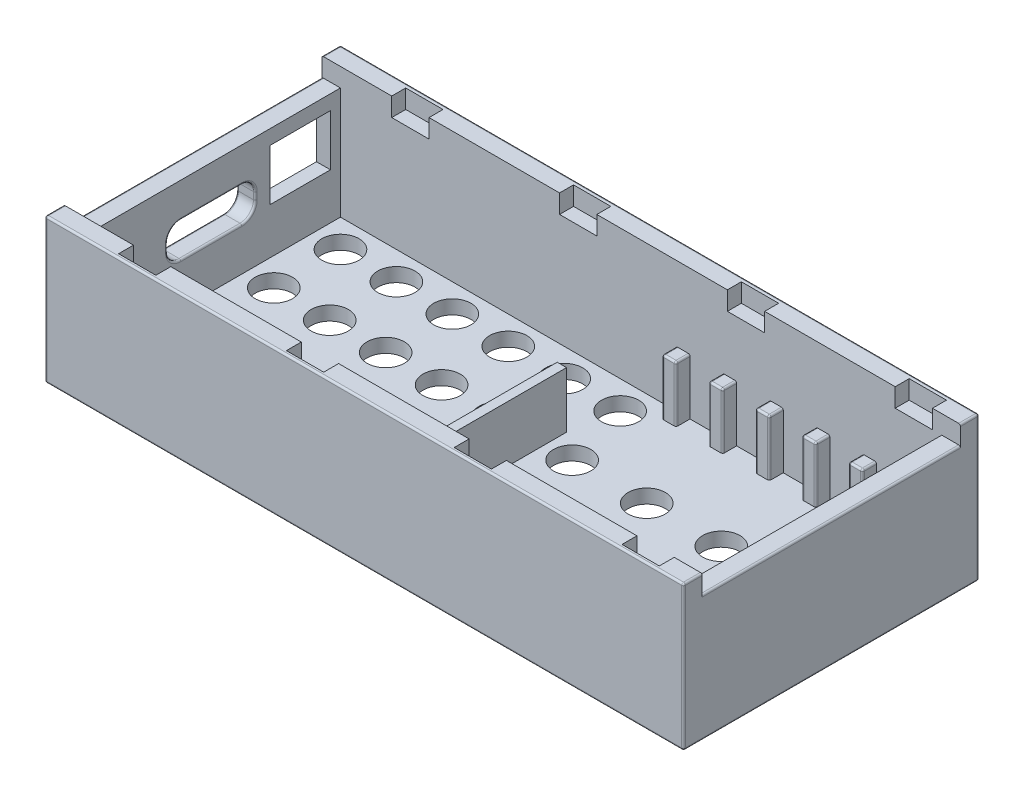
SolidWorks part; units mm, degrees
material "PLA"
ref_plane "前视基准面" through (0, 0, 0) normal (0, 0, 1) x (1, 0, 0)
ref_plane "上视基准面" through (0, 0, 0) normal (0, 1, 0) x (1, 0, 0)
ref_plane "右视基准面" through (0, 0, 0) normal (1, 0, 0) x (0, 0, -1)
sketch "草图1" plane through (0, 0, 0) normal (0, 0, 1) x (1, 0, 0)
  line L0 (0, 0) -> (68.5, 0)
  line L1 (68.5, 0) -> (68.5, 13.5)
  line L2 (68.5, 13.5) -> (66.5, 13.5)
  line L3 (66.5, 13.5) -> (66.5, 1.5)
  line L4 (66.5, 1.5) -> (2, 1.5)
  line L5 (2, 1.5) -> (2, 13.5)
  line L6 (2, 13.5) -> (0, 13.5)
  line L7 (0, 13.5) -> (0, 0)
  dimension "D1" = 64.5
  dimension "D3" = 2
  dimension "D4" = 1.5
  dimension "D6" = 12
extrude "凸台-拉伸1" add sketch "草图1" along normal blind 31.7
sketch "草图3" plane through (0, 1.5, 0) normal (0, 1, 0) x (1, 0, 0)
  line L0 (2, -31.7) -> (66.5, -31.7)
  line L1 (66.5, -31.7) -> (66.5, -29.7)
  line L2 (66.5, -31.7) -> (66.5, 0) construction
  line L3 (66.5, -29.7) -> (2, -29.7)
  line L4 (2, -31.7) -> (2, 0) construction
  line L5 (2, -29.7) -> (2, -31.7)
  dimension "D1" = 2
extrude "凸台-拉伸2" add sketch "草图3" along normal through all
sketch "草图4" plane through (0, 1.5, 0) normal (0, 1, 0) x (1, 0, 0)
  line L0 (2, 0) -> (66.5, 0)
  line L1 (66.5, -29.7) -> (66.5, 0) construction
  line L2 (66.5, -29.7) -> (66.5, 0) construction
  line L3 (66.5, 0) -> (66.5, -2)
  line L4 (66.5, -2) -> (2, -2)
  line L5 (2, -29.7) -> (2, 0) construction
  line L6 (2, -2) -> (2, 0)
  dimension "D1" = 2
extrude "凸台-拉伸3" add sketch "草图4" along normal through all
sketch "草图5" plane through (0, 1.5, 0) normal (0, 1, 0) x (1, 0, 0)
  line L0 (33.6, -6.415) -> (33.6, -25.7073) construction
  line L2 (23.9227, -15.85) -> (46.7103, -15.85) construction
  line L3 (2, -2) -> (66.5, -2) construction
  line L4 (66.5, -29.7) -> (2, -29.7) construction
  line L5 (34.1, -9.85) -> (33.1, -9.85)
  line L6 (33.1, -9.85) -> (33.1, -21.85)
  line L7 (34.1, -9.85) -> (34.1, -21.85)
  line L8 (34.1, -21.85) -> (33.1, -21.85)
  line L9 (2, -29.7) -> (2, -2) construction
  point P14 (33.6, -9.85)
  point P16 (34.1, -15.85)
  point P17 (33.1, -15.85)
  dimension "D1" = 1
  dimension "D2" = 31.6
  dimension "D3" = 12
extrude "凸台-拉伸4" add sketch "草图5" along normal blind 6 contours L6 L8 L7 L5
sketch "草图10" plane through (0, 0, 0) normal (-1, 0, 0) x (0, 0, 1)
  line L0 (5.075, 9.1862) -> (7.575, 9.1862) construction
  line L1 (5.075, 8.1862) -> (5.075, 10.1862) construction
  line L2 (7.575, 10.1862) -> (7.575, 8.1862) construction
  line L3 (6.325, 8.1862) -> (6.325, 10.1862) construction
  line L4 (7.575, 8.1862) -> (5.075, 8.1862) construction
  line L5 (5.075, 10.1862) -> (7.575, 10.1862) construction
  line L7 (8.575, 7.4362) -> (4.075, 7.4362)
  line L8 (8.575, 7.4362) -> (8.575, 10.9362)
  line L9 (8.575, 10.9362) -> (4.075, 10.9362)
  line L10 (4.075, 7.4362) -> (4.075, 10.9362)
  line L11 (8.575, 7.4362) -> (4.075, 10.9362) construction
  line L12 (8.575, 10.9362) -> (4.075, 7.4362) construction
  point P12 (6.325, 9.1862)
  dimension "D1" = 3.5
  dimension "D2" = 4.5
extrude "切除-拉伸3" cut sketch "草图10" against normal up to next
sketch "草图11" plane through (0, 0, 0) normal (-1, 0, 0) x (0, 0, 1)
  line L14 (11.13, 8.3362) -> (11.13, 7.5762)
  line L15 (12.58, 6.1262) -> (19.12, 6.1262)
  line L16 (20.57, 7.5762) -> (20.57, 8.3362)
  line L17 (19.12, 9.7862) -> (12.58, 9.7862)
  line L18 (11.13, 8.3362) -> (11.13, 7.5762)
  line L19 (12.58, 6.1262) -> (19.12, 6.1262)
  line L20 (20.57, 7.5762) -> (20.57, 8.3362)
  line L21 (19.12, 9.7862) -> (12.58, 9.7862)
  arc A8 (11.13, 7.5762) -> (12.58, 6.1262) centre (12.58, 7.5762) ccw
  arc A9 (19.12, 6.1262) -> (20.57, 7.5762) centre (19.12, 7.5762) ccw
  arc A10 (20.57, 8.3362) -> (19.12, 9.7862) centre (19.12, 8.3362) ccw
  arc A11 (12.58, 9.7862) -> (11.13, 8.3362) centre (12.58, 8.3362) ccw
  arc A12 (11.13, 7.5762) -> (12.58, 6.1262) centre (12.58, 7.5762) ccw
  arc A13 (19.12, 6.1262) -> (20.57, 7.5762) centre (19.12, 7.5762) ccw
  arc A14 (20.57, 8.3362) -> (19.12, 9.7862) centre (19.12, 8.3362) ccw
  arc A15 (12.58, 9.7862) -> (11.13, 8.3362) centre (12.58, 8.3362) ccw
  dimension "D1" = 0.3
extrude "切除-拉伸4" cut sketch "草图11" against normal up to next
sketch "草图14" plane through (0, 0, 2) normal (0, 0, 1) x (1, 0, 0)
  line L0 (64.4954, 1.5) -> (64.4954, 7.5)
  line L1 (2, 1.5) -> (66.5, 1.5) construction
  line L2 (64.4954, 7.5) -> (62.9954, 7.5)
  line L3 (62.9954, 7.5) -> (62.9954, 1.5)
  line L4 (62.9954, 1.5) -> (64.4954, 1.5)
  line L5 (66.5, 13.5) -> (66.5, 1.5) construction
  line L6 (62.1133, 1.5) -> (62.1133, 7.9181) construction
  line L7 (57.9954, 7.5) -> (57.9954, 1.5)
  line L8 (59.4954, 7.5) -> (57.9954, 7.5)
  line L9 (59.4954, 1.5) -> (59.4954, 7.5)
  line L10 (57.9954, 1.5) -> (59.4954, 1.5)
  line L11 (52.9954, 7.5) -> (52.9954, 1.5)
  line L12 (54.4954, 7.5) -> (52.9954, 7.5)
  line L13 (54.4954, 1.5) -> (54.4954, 7.5)
  line L14 (52.9954, 1.5) -> (54.4954, 1.5)
  line L15 (47.9954, 7.5) -> (47.9954, 1.5)
  line L16 (49.4954, 7.5) -> (47.9954, 7.5)
  line L17 (49.4954, 1.5) -> (49.4954, 7.5)
  line L18 (47.9954, 1.5) -> (49.4954, 1.5)
  line L19 (42.9954, 7.5) -> (42.9954, 1.5)
  line L20 (44.4954, 7.5) -> (42.9954, 7.5)
  line L21 (44.4954, 1.5) -> (44.4954, 7.5)
  line L22 (42.9954, 1.5) -> (44.4954, 1.5)
  line L23 (37.9954, 7.5) -> (37.9954, 1.5)
  line L24 (39.4954, 7.5) -> (37.9954, 7.5)
  line L25 (39.4954, 1.5) -> (39.4954, 7.5)
  line L26 (37.9954, 1.5) -> (39.4954, 1.5)
  line L27 (62.9954, 7.5) -> (57.9954, 7.5) construction
  dimension "D1" = 1.5
  dimension "D2" = 6
  dimension "D3" = 2.0046
  dimension "D4" = 0.8821
  dimension "D6" = 5
  dimension "D5" = 6
extrude "凸台-拉伸7" add sketch "草图14" along normal blind 1.5
fillet "圆角5" radius 0.2 18 edges at (64.4954, 4.5, 3.5) (63.7454, 7.5, 3.5) (62.9954, 4.5, 3.5) (59.4954, 4.5, 3.5) (58.7454, 7.5, 3.5) (57.9954, 4.5, 3.5) (54.4954, 4.5, 3.5) (53.7454, 7.5, 3.5) (52.9954, 4.5, 3.5) (49.4954, 4.5, 3.5) (48.7454, 7.5, 3.5) (47.9954, 4.5, 3.5) (44.4954, 4.5, 3.5) (43.7454, 7.5, 3.5) (42.9954, 4.5, 3.5) (39.4954, 4.5, 3.5) (38.7454, 7.5, 3.5) (37.9954, 4.5, 3.5)
fillet "圆角6" radius 0.2 24 edges at (64.4368, 7.4414, 3.4414) (63.0539, 7.4414, 3.4414) (58.0539, 7.4414, 3.4414) (59.4368, 7.4414, 3.4414) (54.4368, 7.4414, 3.4414) (49.4368, 7.4414, 3.4414) (44.4368, 7.4414, 3.4414) (39.4368, 7.4414, 3.4414) (53.0539, 7.4414, 3.4414) (48.0539, 7.4414, 3.4414) (43.0539, 7.4414, 3.4414) (38.0539, 7.4414, 3.4414) (64.4954, 7.5, 2.65) (62.9954, 7.5, 2.65) (57.9954, 7.5, 2.65) (59.4954, 7.5, 2.65) (54.4954, 7.5, 2.65) (49.4954, 7.5, 2.65) (44.4954, 7.5, 2.65) (39.4954, 7.5, 2.65) (52.9954, 7.5, 2.65) (47.9954, 7.5, 2.65) (42.9954, 7.5, 2.65) (37.9954, 7.5, 2.65)
sketch "草图15" plane through (0, 0, 29.7) normal (0, 0, -1) x (-1, 0, 0)
  line L0 (-66.5, 1.5) -> (-2, 1.5) construction
  line L1 (-64.5, 1.5) -> (-63, 1.5)
  line L2 (-64.5, 1.5) -> (-64.5, 7.5)
  line L3 (-64.5, 7.5) -> (-63, 7.5)
  line L4 (-63, 1.5) -> (-63, 7.5)
  line L5 (-66.5, 13.5) -> (-66.5, 1.5) construction
  line L6 (-59.5, 1.5) -> (-59.5, 7.5)
  line L7 (-59.5, 7.5) -> (-58, 7.5)
  line L8 (-58, 1.5) -> (-58, 7.5)
  line L9 (-59.5, 1.5) -> (-58, 1.5)
  line L10 (-54.5, 1.5) -> (-54.5, 7.5)
  line L11 (-54.5, 7.5) -> (-53, 7.5)
  line L12 (-53, 1.5) -> (-53, 7.5)
  line L13 (-54.5, 1.5) -> (-53, 1.5)
  line L14 (-49.5, 1.5) -> (-49.5, 7.5)
  line L15 (-49.5, 7.5) -> (-48, 7.5)
  line L16 (-48, 1.5) -> (-48, 7.5)
  line L17 (-49.5, 1.5) -> (-48, 1.5)
  line L18 (-44.5, 1.5) -> (-44.5, 7.5)
  line L19 (-44.5, 7.5) -> (-43, 7.5)
  line L20 (-43, 1.5) -> (-43, 7.5)
  line L21 (-44.5, 1.5) -> (-43, 1.5)
  line L22 (-39.5, 1.5) -> (-39.5, 7.5)
  line L23 (-39.5, 7.5) -> (-38, 7.5)
  line L24 (-38, 1.5) -> (-38, 7.5)
  line L25 (-39.5, 1.5) -> (-38, 1.5)
  line L26 (-64.5, 1.5) -> (-59.5, 1.5) construction
  dimension "D1" = 2
  dimension "D2" = 1.5
  dimension "D3" = 6
  dimension "D5" = 5
  dimension "D4" = 6
extrude "凸台-拉伸8" add sketch "草图15" along normal blind 1.5
fillet "圆角7" radius 0.2 30 edges at (38, 7.5, 28.95) (38.75, 7.5, 28.2) (38, 4.5, 28.2) (39.5, 4.5, 28.2) (39.5, 7.5, 28.95) (43, 4.5, 28.2) (44.5, 4.5, 28.2) (43, 7.5, 28.95) (43.75, 7.5, 28.2) (44.5, 7.5, 28.95) (48, 7.5, 28.95) (48, 4.5, 28.2) (48.75, 7.5, 28.2) (49.5, 4.5, 28.2) (49.5, 7.5, 28.95) (53, 7.5, 28.95) (53.75, 7.5, 28.2) (53, 4.5, 28.2) (54.5, 4.5, 28.2) (54.5, 7.5, 28.95) (59.5, 7.5, 28.95) (58, 7.5, 28.95) (58.75, 7.5, 28.2) (58, 4.5, 28.2) (59.5, 4.5, 28.2) (64.5, 4.5, 28.2) (63, 4.5, 28.2) (63, 7.5, 28.95) (63.75, 7.5, 28.2) (64.5, 7.5, 28.95)
sketch "草图16" plane through (0, 0, 0) normal (-1, 0, 0) x (0, 0, 1)
  line L0 (0, 13.5) -> (0, 15.5)
  line L1 (0, 15.5) -> (2, 15.5)
  line L2 (2, 15.5) -> (2, 13.5)
  line L3 (31.7, 13.5) -> (0, 13.5) construction
  line L4 (2, 13.5) -> (0, 13.5)
  line L5 (15.85, 0) -> (15.85, 20.1555) construction
  line L6 (31.7, 0) -> (0, 0) construction
  line L7 (29.7, 13.5) -> (31.7, 13.5)
  line L8 (29.7, 15.5) -> (29.7, 13.5)
  line L9 (31.7, 15.5) -> (29.7, 15.5)
  line L10 (31.7, 13.5) -> (31.7, 15.5)
  dimension "D1" = 2
  dimension "D2" = 2
extrude "凸台-拉伸9" add sketch "草图16" against normal through all
fillet "圆角8" radius 0.2 8 edges at (0, 6.5509, 20.1453) (0, 6.1262, 15.85) (0, 6.5509, 11.5547) (0, 7.9562, 11.13) (0, 9.3615, 11.5547) (0, 9.7862, 15.85) (0, 9.3615, 20.1453) (0, 7.9562, 20.57)
fillet "圆角9" radius 0.2 4 edges at (68.5, 13.5, 15.85) (0, 13.5, 15.85) (34.25, 15.5, 0) (34.25, 15.5, 31.7)
fillet "圆角10" radius 0.2 16 edges at (68.5, 15.5, 1.1) (68.5, 15.4414, 0.0586) (68.5, 15.5, 30.6) (68.5, 15.4414, 31.6414) (0, 15.5, 30.6) (0, 15.4414, 31.6414) (0, 15.5, 1.1) (0, 15.4414, 0.0586) (34.25, 0, 0) (68.5, 0, 15.85) (68.5, 7.65, 0) (68.5, 7.65, 31.7) (34.25, 0, 31.7) (0, 7.65, 31.7) (0, 0, 15.85) (0, 7.65, 0)
fillet "圆角11" radius 0.2 8 edges at (2, 6.5509, 20.1453) (2, 7.9562, 20.57) (2, 9.3615, 20.1453) (2, 9.7862, 15.85) (2, 9.3615, 11.5547) (2, 7.9562, 11.13) (2, 6.5509, 11.5547) (2, 6.1262, 15.85)
sketch "草图17" plane through (0, 0, 0) normal (-1, 0, 0) x (0, 0, 1)
  line L8 (9.575, 6.4362) -> (9.575, 11.9362)
  line L9 (3.075, 6.4362) -> (9.575, 6.4362)
  line L10 (3.075, 11.9362) -> (3.075, 6.4362)
  line L11 (9.575, 11.9362) -> (3.075, 11.9362)
  line L12 (9.575, 6.4362) -> (9.575, 11.9362)
  line L13 (3.075, 6.4362) -> (9.575, 6.4362)
  line L14 (3.075, 11.9362) -> (3.075, 6.4362)
  line L15 (9.575, 11.9362) -> (3.075, 11.9362)
  dimension "D1" = 1
extrude "切除-拉伸5" cut sketch "草图17" against normal up to next
chamfer "倒角1" distance 0.5 angle 45 4 edges at (0, 9.1862, 9.575) (0, 11.9362, 6.325) (0, 9.1862, 3.075) (0, 6.4362, 6.325)
ref_plane "基准面1" through (0, 0, 15.85) normal (0, 0, -1) x (-1, 0, 0)
sketch "草图19" plane through (0, 15.5, 0) normal (0, 1, 0) x (1, 0, 0)
  line L0 (68.3, -2) -> (0.2, -2) construction
  line L1 (65.5, -2) -> (61.5, -2)
  line L2 (65.5, -2) -> (65.5, -0.5)
  line L3 (65.5, -0.5) -> (61.5, -0.5)
  line L4 (61.5, -2) -> (61.5, -0.5)
  line L5 (68.5, -0.2) -> (68.5, -2) construction
  line L6 (47.5, -2) -> (47.5, -0.5)
  line L7 (47.5, -2) -> (43.5, -2)
  line L8 (43.5, -2) -> (43.5, -0.5)
  line L9 (47.5, -0.5) -> (43.5, -0.5)
  line L10 (29.5, -2) -> (29.5, -0.5)
  line L11 (29.5, -2) -> (25.5, -2)
  line L12 (25.5, -2) -> (25.5, -0.5)
  line L13 (29.5, -0.5) -> (25.5, -0.5)
  line L14 (11.5, -2) -> (11.5, -0.5)
  line L15 (11.5, -2) -> (7.5, -2)
  line L16 (7.5, -2) -> (7.5, -0.5)
  line L17 (11.5, -0.5) -> (7.5, -0.5)
  line L18 (65.5, -2) -> (47.5, -2) construction
  dimension "D1" = 3
  dimension "D2" = 1.5
  dimension "D3" = 4
  dimension "D5" = 18
  dimension "D4" = 4
extrude "切除-拉伸6" cut sketch "草图19" against normal blind 2
sketch "草图21" plane through (0, 0, 29.7) normal (0, 0, -1) x (-1, 0, 0)
  line L0 (-43.5, 15.5) -> (-47.5, 15.5)
  line L1 (-47.5, 15.5) -> (-47.5, 13.5)
  line L2 (-47.5, 13.5) -> (-43.5, 13.5)
  line L3 (-43.5, 13.5) -> (-43.5, 15.5)
  line L4 (-61.5, 15.5) -> (-65.5, 15.5)
  line L5 (-61.5, 13.5) -> (-61.5, 15.5)
  line L6 (-65.5, 13.5) -> (-61.5, 13.5)
  line L7 (-65.5, 15.5) -> (-65.5, 13.5)
  line L8 (-61.5, 15.5) -> (-65.5, 15.5)
  line L9 (-61.5, 13.5) -> (-61.5, 15.5)
  line L10 (-65.5, 13.5) -> (-61.5, 13.5)
  line L11 (-65.5, 15.5) -> (-65.5, 13.5)
  line L12 (-25.5, 15.5) -> (-29.5, 15.5)
  line L13 (-29.5, 15.5) -> (-29.5, 13.5)
  line L14 (-29.5, 13.5) -> (-25.5, 13.5)
  line L15 (-25.5, 13.5) -> (-25.5, 15.5)
  line L16 (-7.5, 15.5) -> (-11.5, 15.5)
  line L17 (-11.5, 15.5) -> (-11.5, 13.5)
  line L18 (-11.5, 13.5) -> (-7.5, 13.5)
  line L19 (-7.5, 13.5) -> (-7.5, 15.5)
  line L20 (-61.5, 15.5) -> (-43.5, 15.5) construction
  dimension "D3" = 18
  dimension "D1" = 0
  dimension "D2" = 4
extrude "切除-拉伸8" cut sketch "草图21" against normal blind 1.6
sketch "草图23" plane through (0, 1.5, 0) normal (0, 1, 0) x (1, 0, 0)
  line L1 (5, -12.15) -> (11, -12.15) construction
  line L2 (5, -26.45) -> (11, -26.45) construction
  line L3 (29, -12.15) -> (37, -12.15) construction
  line L4 (29, -19.3) -> (37, -19.3) construction
  circle A0 centre (5, -5) radius 2
  circle A1 centre (11, -5) radius 2
  circle A2 centre (17, -5) radius 2
  circle A3 centre (23, -5) radius 2
  circle A4 centre (29, -5) radius 2
  circle A5 centre (35, -5) radius 2
  circle A6 centre (5, -12.15) radius 2
  circle A7 centre (5, -19.3) radius 2
  circle A8 centre (5, -26.45) radius 2
  circle A9 centre (11, -12.15) radius 2
  circle A10 centre (11, -19.3) radius 2
  circle A11 centre (17, -12.15) radius 2
  circle A12 centre (17, -19.3) radius 2
  circle A13 centre (23, -12.15) radius 2
  circle A14 centre (23, -19.3) radius 2
  circle A15 centre (29, -12.15) radius 2
  circle A16 centre (29, -19.3) radius 2
  circle A17 centre (11, -26.45) radius 2
  circle A18 centre (17, -26.45) radius 2
  circle A19 centre (23, -26.45) radius 2
  circle A20 centre (29, -26.45) radius 2
  circle A21 centre (35, -26.45) radius 2
  circle A22 centre (37, -12.15) radius 2
  circle A23 centre (45, -12.15) radius 2
  circle A24 centre (53, -12.15) radius 2
  circle A25 centre (61, -12.15) radius 2
  circle A26 centre (37, -19.3) radius 2
  circle A27 centre (45, -19.3) radius 2
  circle A28 centre (53, -19.3) radius 2
  circle A29 centre (61, -19.3) radius 2
  dimension "D1" = 4
  dimension "D3" = 5
  dimension "D8" = 5
  dimension "D2" = 5
  dimension "D5" = 6
  dimension "D7" = 7.15
  dimension "D9" = 6
  dimension "D11" = 6
  dimension "D13" = 8
  dimension "D15" = 8
  dimension "D4" = 6
  dimension "D6" = 4
  dimension "D10" = 6
  dimension "D12" = 5
  dimension "D14" = 5
extrude "切除-拉伸9" cut sketch "草图23" against normal up to next (1.5 mm away)
